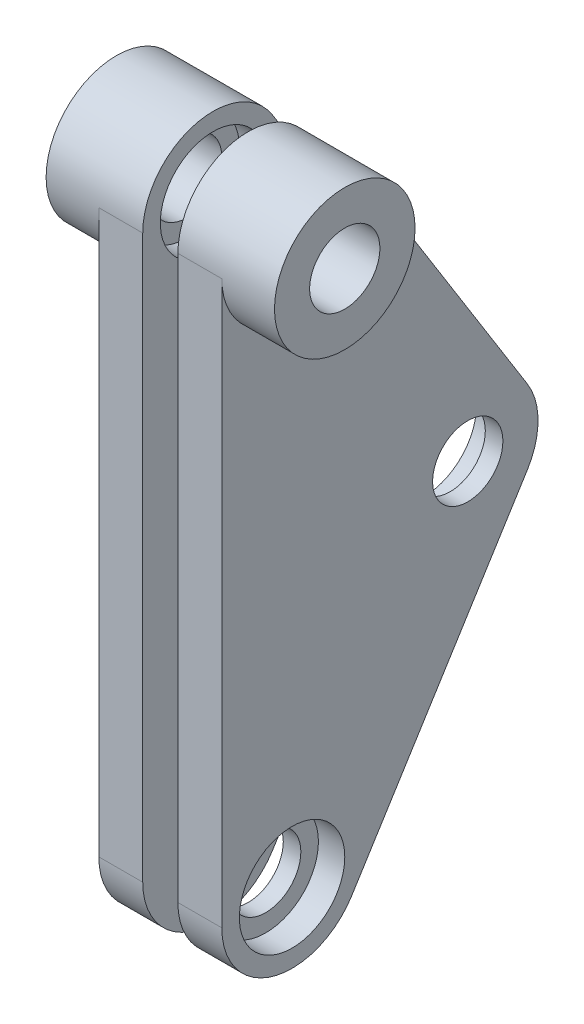
SolidWorks part; units mm, degrees
ref_plane "前视基准面" through (0, 0, 0) normal (0, 0, 1) x (1, 0, 0)
ref_plane "上视基准面" through (0, 0, 0) normal (0, 1, 0) x (1, 0, 0)
ref_plane "右视基准面" through (0, 0, 0) normal (1, 0, 0) x (0, 0, -1)
other "Configuration Table"
sketch "草图1" plane through (0, 0, 0) normal (1, 0, 0) x (0, 0, -1)
  line L0 (0, -20) -> (18, -20) construction
  line L1 (0, 0) -> (18, 0) construction
  line L2 (0, 0) -> (0, -40)
  line L3 (0, -40) -> (18, -40) construction
  line L4 (18, 0) -> (18, -40) construction
  line L5 (7.392, -1.88) -> (17.392, -17.88)
  line L6 (17.392, -22.12) -> (7.392, -38.12)
  circle A0 centre (4, -4) radius 4
  circle A1 centre (4, -36) radius 4
  circle A2 centre (14, -20) radius 4
  circle A3 centre (4, -4) radius 2
  circle A4 centre (14, -20) radius 2
  circle A5 centre (4, -36) radius 2
  dimension "D1" = 8
  dimension "D2" = 4
  dimension "D3" = 40
  dimension "D4" = 18
extrude "凸台-拉伸1" add sketch "草图1" along normal blind 2.5 contours A2 L5 A0 L2 A1 L6 | A0 | A2 | A1 region at (0, -20, -6.5849)
extrude "凸台-拉伸2" add sketch "草图1<4>" against normal blind 3 contours A0
sketch "草图1<4>" plane through (0, 0, 0) normal (1, 0, 0) x (0, 0, -1) same geometry as "草图1"
extrude "切除-拉伸1" cut sketch "草图1<3>" along normal through all both and the other way through all contours A3 | A4 | A5
sketch "草图1<3>" plane through (0, 0, 0) normal (1, 0, 0) x (0, 0, -1) same geometry as "草图1"
sketch "草图2" plane through (2.5, 0, 0) normal (1, 0, 0) x (0, 0, -1)
  circle A0 centre (4, -4) radius 3
  circle A1 centre (14, -20) radius 3
  circle A2 centre (4, -36) radius 3
  circle M3 centre (4, -4) radius 2
  arc M9 (7.392, -1.88) -> (0, -4) centre (4, -4) ccw
  dimension "D1" = 6
extrude "切除-拉伸2" cut sketch "草图2" against normal blind 1.5 contours A0 M9 M3 | A1 region at (2.5, -4, -1.0849)
extrude "切除-拉伸3" cut sketch "草图2<3>" along normal blind 1.5 from surface contours A2 starting at face at (0, -20, -16)
sketch "草图2<3>" plane through (2.5, 0, 0) normal (1, 0, 0) x (0, 0, -1) same geometry as "草图2"
ref_plane "基准面1" through (3.5, 0, 0) normal (1, 0, 0) x (0, 0, -1)
mirror "镜向2" about plane through (3.5, 0, 0) normal (1, 0, 0) of bodies 111 109
